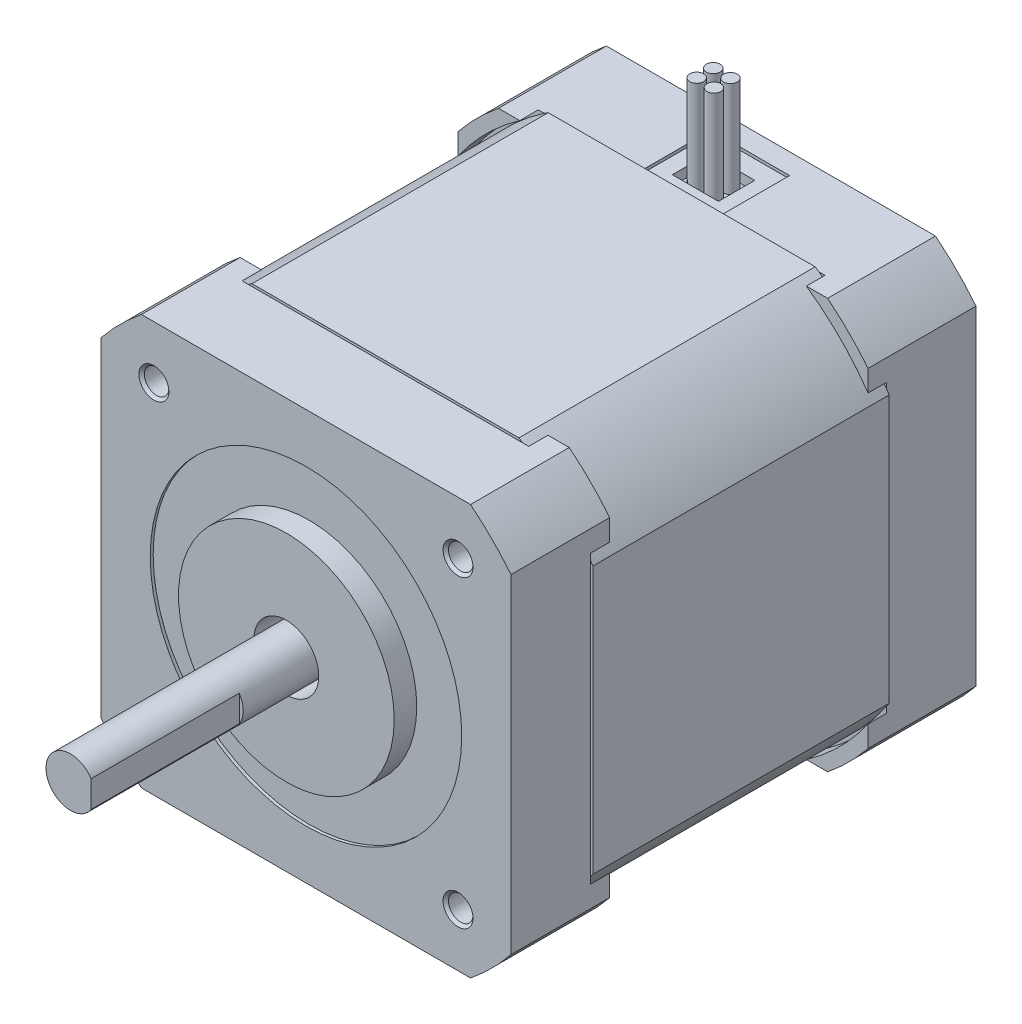
SolidWorks part; units mm, degrees
ref_plane "Спереди" through (0, 0, 0) normal (0, 0, 1) x (1, 0, 0)
ref_plane "Сверху" through (0, 0, 0) normal (0, 1, 0) x (1, 0, 0)
ref_plane "Справа" through (0, 0, 0) normal (1, 0, 0) x (0, 0, -1)
sketch "Эскиз1" plane through (0, 0, 0) normal (0, 0, 1) x (1, 0, 0)
  line L1 (20.9, 20.9) -> (-20.9, 20.9)
  line L2 (20.9, 20.9) -> (20.9, -20.9)
  line L3 (20.9, -20.9) -> (-20.9, -20.9)
  line L4 (-20.9, 20.9) -> (-20.9, -20.9)
  line L5 (0, -20.9) -> (0, 20.9) construction
  line L6 (20.9, 0) -> (-20.9, 0) construction
  circle A0 centre (0, 0) radius 26.8
  point P0 (0, 0)
  dimension "D2" = 53.6
  dimension "D1" = 41.8
extrude "Бобышка-Вытянуть1" add sketch "Эскиз1" along normal blind 11 contours L2 A0 L1 L4 L3 region at (0, 0, 0)
sketch "Эскиз2" plane through (0, 0, 11) normal (0, 0, 1) x (1, 0, 0)
  circle A0 centre (0, 0) radius 25.5
  dimension "D1" = 51
extrude "Вырез-Вытянуть1" cut sketch "Эскиз2" against normal blind 1.9
sketch "Эскиз3" plane through (0, 0, 9.1) normal (0, 0, 1) x (1, 0, 0)
  line L1 (21.15, 21.15) -> (-21.15, 21.15)
  line L2 (21.15, 21.15) -> (21.15, -21.15)
  line L3 (21.15, -21.15) -> (-21.15, -21.15)
  line L4 (-21.15, 21.15) -> (-21.15, -21.15)
  line L5 (0, -21.15) -> (0, 21.15) construction
  line L6 (21.15, 0) -> (-21.15, 0) construction
  circle A0 centre (0, 0) radius 25.15
  line M2 (14.6096, 20.9) -> (-14.6096, 20.9)
  line M4 (-20.9, 14.6096) -> (-20.9, -14.6096)
  line M6 (-14.6096, -20.9) -> (14.6096, -20.9)
  line M8 (20.9, -14.6096) -> (20.9, 14.6096)
  dimension "D1" = 50.3
  dimension "D2" = 42.3
extrude "Бобышка-Вытянуть2" add sketch "Эскиз3" along normal blind 30.2 contours A0 M8 M2 M4 M6 | A0 L1 M2 | L2 A0 M8 | A0 L3 M6 | A0 L4 M4 region at (0, 21.0244, 9.1) region at (21.0244, 0, 9.1) region at (0, 0, 9.1) region at (-21.0244, 0, 9.1) region at (0, -21.0244, 9.1)
extrude "Бобышка-Вытянуть3" add sketch "Эскиз1<3>" along normal offset from surface (8.1 mm away) 47.4 from surface contours L2 A0 L1 L4 L3 region at (0, 0, 0) up to face at (0, 0, 0) starting at face at (0, 0, 39.3)
sketch "Эскиз1<3>" plane through (0, 0, 0) normal (0, 0, 1) x (1, 0, 0) same geometry as "Эскиз1"
sketch "Эскиз4" plane through (0, 0, 39.3) normal (0, 0, -1) x (-1, 0, 0)
  line L0 (14.6096, 20.9) -> (16.7759, 20.9) construction
  line L1 (20.9, 16.7759) -> (20.9, 14.6096) construction
  line L2 (20.9, -14.6096) -> (20.9, -16.7759) construction
  line L3 (16.7759, -20.9) -> (14.6096, -20.9) construction
  line L4 (-14.6096, -20.9) -> (-16.7759, -20.9) construction
  line L5 (-20.9, -16.7759) -> (-20.9, -14.6096) construction
  line L6 (-20.9, 14.6096) -> (-20.9, 16.7759) construction
  line L7 (-16.7759, 20.9) -> (-14.6096, 20.9) construction
  line L8 (14.6096, 20.9) -> (16.7759, 20.9)
  line L9 (20.9, 16.7759) -> (20.9, 14.6096)
  line L10 (20.9, -14.6096) -> (20.9, -16.7759)
  line L11 (16.7759, -20.9) -> (14.6096, -20.9)
  line L12 (-14.6096, -20.9) -> (-16.7759, -20.9)
  line L13 (-20.9, -16.7759) -> (-20.9, -14.6096)
  line L14 (-20.9, 14.6096) -> (-20.9, 16.7759)
  line L15 (-16.7759, 20.9) -> (-14.6096, 20.9)
  arc A0 (20.9, 14.6096) -> (14.6096, 20.9) centre (0, 0) ccw construction
  arc A1 (20.9, 16.7759) -> (16.7759, 20.9) centre (0, 0) ccw construction
  arc A2 (14.6096, -20.9) -> (20.9, -14.6096) centre (0, 0) ccw construction
  arc A3 (16.7759, -20.9) -> (20.9, -16.7759) centre (0, 0) ccw construction
  arc A4 (-20.9, -14.6096) -> (-14.6096, -20.9) centre (0, 0) ccw construction
  arc A5 (-20.9, -16.7759) -> (-16.7759, -20.9) centre (0, 0) ccw construction
  arc A6 (-14.6096, 20.9) -> (-20.9, 14.6096) centre (0, 0) ccw construction
  arc A7 (-16.7759, 20.9) -> (-20.9, 16.7759) centre (0, 0) ccw construction
  arc A8 (20.9, 14.6096) -> (14.6096, 20.9) centre (0, 0) ccw
  arc A9 (20.9, 16.7759) -> (16.7759, 20.9) centre (0, 0) ccw
  arc A10 (14.6096, -20.9) -> (20.9, -14.6096) centre (0, 0) ccw
  arc A11 (16.7759, -20.9) -> (20.9, -16.7759) centre (0, 0) ccw
  arc A12 (-20.9, -14.6096) -> (-14.6096, -20.9) centre (0, 0) ccw
  arc A13 (-20.9, -16.7759) -> (-16.7759, -20.9) centre (0, 0) ccw
  arc A14 (-14.6096, 20.9) -> (-20.9, 14.6096) centre (0, 0) ccw
  arc A15 (-16.7759, 20.9) -> (-20.9, 16.7759) centre (0, 0) ccw
extrude "Бобышка-Вытянуть4" add sketch "Эскиз4" along normal blind 1.96
sketch "Эскиз5" plane through (0, 0, 47.4) normal (0, 0, 1) x (1, 0, 0)
  circle A0 centre (0, 0) radius 15.875
  dimension "D1" = 31.75
extrude "Вырез-Вытянуть2" cut sketch "Эскиз5" against normal blind 0.3
sketch "Эскиз6" plane through (0, 0, 47.1) normal (0, 0, 1) x (1, 0, 0)
  circle A0 centre (0, 0) radius 10.995
  dimension "D1" = 21.99
extrude "Бобышка-Вытянуть5" add sketch "Эскиз6" along normal blind 2.3
sketch "Эскиз7" plane through (0, 0, 49.4) normal (0, 0, 1) x (1, 0, 0)
  circle A0 centre (0, 0) radius 3.3
  dimension "D1" = 6.6
extrude "Вырез-Вытянуть3" cut sketch "Эскиз7" against normal blind 5
sketch "Эскиз8" plane through (0, 0, 44.4) normal (0, 0, 1) x (1, 0, 0)
  circle A0 centre (0, 0) radius 2.5
  dimension "D1" = 5
extrude "Бобышка-Вытянуть7" add sketch "Эскиз8" along normal offset from surface (27 mm away) 22 up to face at (3.3, 0, 49.4) offset beyond the face yes
sketch "Эскиз9" plane through (0, 0, 71.4) normal (0, 0, 1) x (1, 0, 0)
  line L1 (2.1, 1.3565) -> (2.5, 1.3565)
  line L2 (2.1, 1.3565) -> (2.1, -1.3565)
  line L3 (2.1, -1.3565) -> (2.5, -1.3565)
  line L4 (2.5, 1.3565) -> (2.5, -1.3565)
  circle A0 centre (0, 0) radius 2.5 construction
  dimension "D1" = 4.6
extrude "Вырез-Вытянуть4" cut sketch "Эскиз9" against normal blind 15.1
hole_wizard "M3 Tapped Hole1" positions "Эскиз10" profile "Эскиз11" tap size "M3" standard "DIN"
sketch "Эскиз10" plane through (0, 0, 47.4) normal (0, 0, 1) x (1, 0, 0)
  point P0 (-15.5, 15.5)
  dimension "D1" = 15.5
  dimension "D2" = 15.5
sketch "Эскиз11" plane through (-15.5, 15.5, 47.4) normal (1, 0, 0) x (0, -1, 0)
  line L0 (0, 0) -> (0, 6.7511)
  line L1 (0, 6.7511) -> (1.25, 6)
  line L2 (1.25, 6) -> (1.25, 0.275)
  line L3 (1.25, 0.275) -> (1.525, 0)
  line L5 (1.525, 0) -> (0, 0)
  line L6 (-1.25, 0.275) -> (-1.525, 0) construction
  line L10 (0, 6.7511) -> (-1.25, 6) construction
  line L11 (0, -6.35) -> (0, 107.95) construction
  dimension "Диаметр сверла" = 2.5
  dimension "Глубина сверла" = 6
  dimension "Диаметр передней зенковки" = 3.05
  dimension "Угол передней зенковки" = 90
  dimension "Угол заточки сверла" = 118
cosmetic thread "Отверстие резьбы1" parameters "D1"=4.5, "D2"=3
sketch "Эскиз12" plane through (0, 0, 0) normal (0, 0, -1) x (-1, 0, 0)
  circle A0 centre (15.5, 15.5) radius 3
  dimension "D1" = 6
extrude "Вырез-Вытянуть5" cut sketch "Эскиз12" against normal blind 0.3
sketch "Эскиз13" plane through (0, 0, 0.3) normal (0, 0, -1) x (-1, 0, 0)
  line L1 (15.0809, 17.4616) -> (15.9191, 17.4616)
  line L2 (15.0809, 17.4616) -> (15.0809, 13.5384)
  line L3 (15.0809, 13.5384) -> (15.9191, 13.5384)
  line L4 (15.9191, 17.4616) -> (15.9191, 13.5384)
  line L5 (15.5, 13.5384) -> (15.5, 17.4616) construction
  line L6 (15.0809, 15.5) -> (15.9191, 15.5) construction
  line L7 (13.5384, 15.9191) -> (17.4616, 15.9191)
  line L8 (13.5384, 15.9191) -> (13.5384, 15.0809)
  line L9 (13.5384, 15.0809) -> (17.4616, 15.0809)
  line L10 (17.4616, 15.9191) -> (17.4616, 15.0809)
  line L11 (15.5, 15.0809) -> (15.5, 15.9191) construction
  line L12 (13.5384, 15.5) -> (17.4616, 15.5) construction
  point P0 (15.5, 15.5)
  point P4 (15.5, 15.5)
extrude "Вырез-Вытянуть6" cut sketch "Эскиз13" against normal blind 2 contours L8 L9 L2 L7 | L2 L7 L4 L1 | L2 L9 L4 L7 | L10 L7 L4 L9 | L9 L2 L3 L4 region at (-15.5, 16.6903, 0.3) region at (-15.5, 15.5, 0.3) region at (-14.3097, 15.5, 0.3) region at (-16.6903, 15.5, 0.3) region at (-15.5, 14.3097, 0.3)
chamfer "Фаска1" distance 1.54 angle 45 4 edges at (-13.5384, 15.5, 2.3) (-15.5, 13.5384, 2.3) (-17.4616, 15.5, 2.3) (-15.5, 17.4616, 2.3)
fillet "Скругление1" radius 0.5 4 edges at (-15.0809, 15.0809, 1.3) (-15.9191, 15.0809, 1.3) (-15.0809, 15.9191, 1.3) (-15.9191, 15.9191, 1.3)
pattern_circular "Круговой массив1" count 4 over 360 about axis through (0, 0, 100.4711) along (0, 0, -1) of "M3 Tapped Hole1", "Вырез-Вытянуть5", "Вырез-Вытянуть6", "Фаска1", "Скругление1" reverse direction yes
cosmetic thread "Отверстие резьбы2" parameters "D1"=4.5, "D2"=3
cosmetic thread "Отверстие резьбы3" parameters "D1"=4.5, "D2"=3
cosmetic thread "Отверстие резьбы4" parameters "D1"=4.5, "D2"=3
sketch "Эскиз14" plane through (0, 20.9, 0) normal (0, 1, 0) x (1, 0, 0)
  line L0 (13.9897, -9.1) -> (-13.9897, -9.1) construction
  line L1 (-4, -2.1) -> (4, -2.1)
  line L2 (-4, -2.1) -> (-4, -9.1)
  line L3 (-4, -9.1) -> (4, -9.1)
  line L4 (4, -2.1) -> (4, -9.1)
  point P4 (0, -9.1)
  dimension "D1" = 8
  dimension "D2" = 7
extrude "Вырез-Вытянуть7" cut sketch "Эскиз14" against normal blind 0.3
sketch "Эскиз15" plane through (0, 20.6, 0) normal (0, 1, 0) x (1, 0, 0)
  line L0 (16.7759, 0) -> (-16.7759, 0) construction
  line L1 (-2.35, -4) -> (2.35, -4)
  line L2 (-2.35, -4) -> (-2.35, -7.7)
  line L3 (-2.35, -7.7) -> (2.35, -7.7)
  line L4 (2.35, -4) -> (2.35, -7.7)
  point P4 (0, -7.7)
  dimension "D1" = 3.7
  dimension "D2" = 4.7
  dimension "D3" = 4
extrude "Вырез-Вытянуть8" cut sketch "Эскиз15" against normal blind 1
sketch "Эскиз16" plane through (0, 19.6, 0) normal (0, 1, 0) x (1, 0, 0)
  line L0 (0, -7.7) -> (0, -4) construction
  line L1 (-2.35, -7.7) -> (2.35, -7.7) construction
  line L2 (2.35, -4) -> (-2.35, -4) construction
  line L3 (2.35, -5.85) -> (-2.35, -5.85) construction
  line L4 (2.35, -7.7) -> (2.35, -4) construction
  line L5 (-2.35, -4) -> (-2.35, -7.7) construction
  circle A0 centre (-0.8763, -6.6921) radius 0.7
  circle A1 centre (0.8763, -6.6921) radius 0.7
  circle A2 centre (0.8763, -5.0079) radius 0.7
  circle A3 centre (-0.8763, -5.0079) radius 0.7
  dimension "D1" = 1.4
extrude "Бобышка-Вытянуть8" add sketch "Эскиз16" along normal blind 9.8
